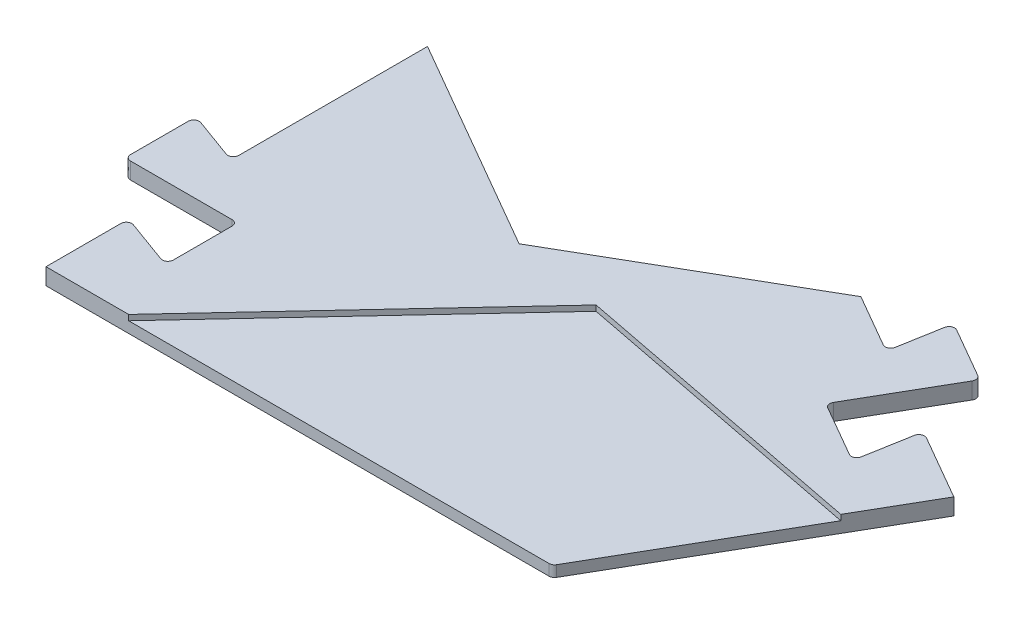
SolidWorks part; units mm, degrees
ref_plane "Přední rovina" through (0, 0, 0) normal (0, 0, 1) x (1, 0, 0)
ref_plane "Horní rovina" through (0, 0, 0) normal (0, 1, 0) x (1, 0, 0)
ref_plane "Pravá rovina" through (0, 0, 0) normal (1, 0, 0) x (0, 0, -1)
sketch "Skica1" plane through (0, 0, 0) normal (0, 1, 0) x (1, 0, 0)
  line L0 (105.5337, 53.6901) -> (118.5241, 46.1901)
  line L1 (118.5241, 46.1901) -> (91.8562, 0)
  line L2 (15, 0) -> (55.9106, 43.8899)
  line L3 (0, 0) -> (0, 15)
  line L4 (0, 15) -> (10.5, 11.1783)
  line L5 (10.5, 11.1783) -> (10.5, 24.2783)
  line L6 (10.5, 24.2783) -> (-9.9505, 24.2783)
  line L7 (55.9106, 43.8899) -> (111.0185, 33.1901)
  line L8 (0, 0) -> (91.8562, 0)
  line L9 (0, 33.5566) -> (-9.9505, 37.1783)
  line L10 (-9.9505, 37.1783) -> (-9.9505, 24.2783)
  line L11 (0, 69.22) -> (0, 33.5566)
  line L12 (0, 69.22) -> (39.3176, 46.52)
  line L13 (39.3176, 46.52) -> (78.6351, 69.22)
  line L14 (105.5337, 53.6901) -> (103.5934, 42.686)
  line L15 (103.5934, 42.686) -> (92.2485, 49.236)
  line L16 (78.6351, 69.22) -> (89.4632, 62.9684)
  line L17 (92.2485, 49.236) -> (102.4737, 66.9466)
  line L18 (89.4632, 62.9684) -> (91.302, 73.3966)
  line L19 (91.302, 73.3966) -> (102.4737, 66.9466)
  line L20 (0, 69.22) -> (0, 0) construction
  line L21 (78.6351, 69.22) -> (118.5241, 46.1901) construction
  point P0 (94.9308, 5.3253)
  dimension "D1" = 90
  dimension "D2" = 15
  dimension "D3" = 91.8562
  dimension "D4" = 70
  dimension "D5" = 15
  dimension "D6" = 122
  dimension "D7" = 69.22
  dimension "D8" = 60
  dimension "D9" = 13
  dimension "D10" = 120
  dimension "D11" = 45.4
  dimension "D12" = 45.4
  dimension "D13" = 69.22
  dimension "D14" = 70
  dimension "D15" = 70
  dimension "D16" = 120
  dimension "D17" = 120
  dimension "D18" = 13.1
  dimension "D19" = 12.9
  dimension "D20" = 10.5
  dimension "D21" = 12.9
  dimension "D22" = 13.1
  dimension "D23" = 10.5
  dimension "D24" = 15
extrude "Přidat vysunutím1" add sketch "Skica1" along normal blind 3 contours L19 L18 L16 L13 L12 L11 L9 L10 L6 L5 L4 L3 L8 L2 L7 L1 L0 L14 L15 L17 region at (43.6515, 0, -40.5739)
extrude "Přidat vysunutím2" add sketch "Skica1<3>" along normal blind 2 contours L2 L8 L1 L7 region at (66.2955, 0, -18.7917)
sketch "Skica1<3>" plane through (0, 0, 0) normal (0, 1, 0) x (1, 0, 0) same geometry as "Skica1"
fillet "Zaoblit1" radius 1 12 edges at (0, 1.5, -33.5566) (-9.9505, 1.5, -37.1783) (10.5, 1.5, -24.2783) (-9.9505, 1.5, -24.2783) (10.5, 1.5, -11.1783) (0, 1.5, -15) (105.5337, 1.5, -53.6901) (103.5934, 1.5, -42.686) (92.2485, 1.5, -49.236) (89.4632, 1.5, -62.9684) (91.302, 1.5, -73.3966) (102.4737, 1.5, -66.9466)
fillet "Zaoblit2" radius 1 1 edges at (91.8562, 1, 0)
